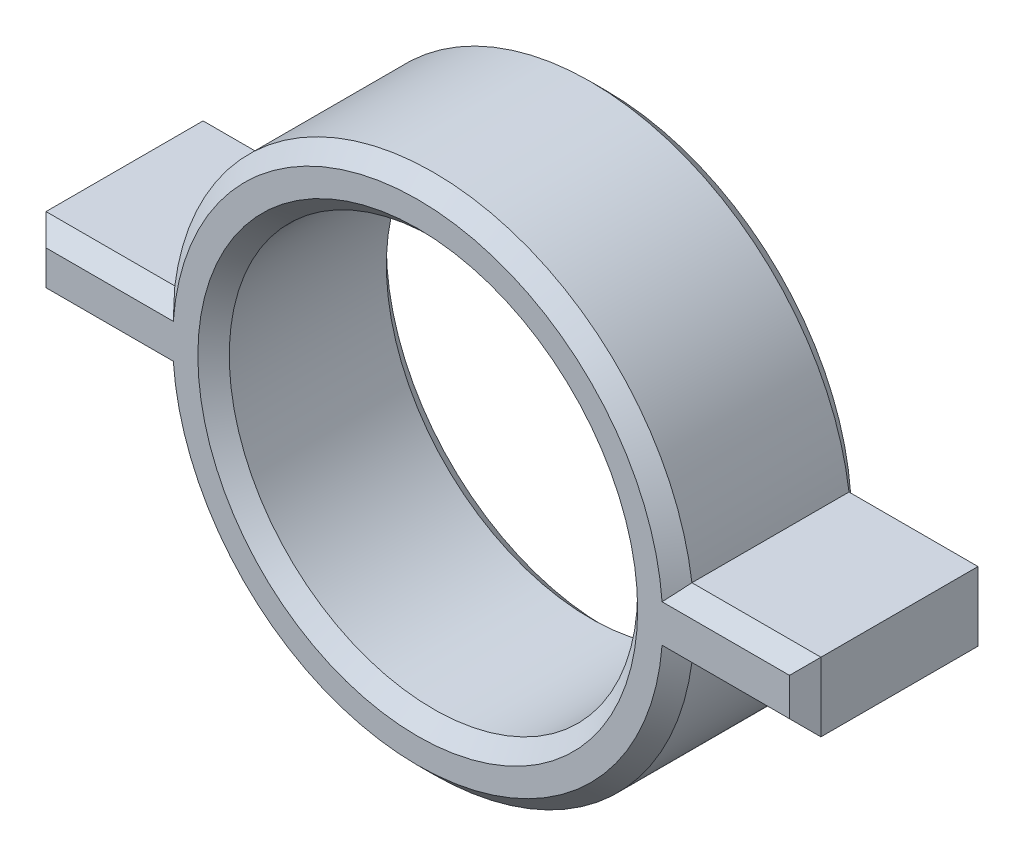
SolidWorks part; units mm, degrees
material "PLA"
ref_plane "Front Plane" through (0, 0, 0) normal (0, 0, 1) x (1, 0, 0)
ref_plane "Top Plane" through (0, 0, 0) normal (0, 1, 0) x (1, 0, 0)
ref_plane "Right Plane" through (0, 0, 0) normal (1, 0, 0) x (0, 0, -1)
sketch "Sketch1" plane through (0, 0, 0) normal (0, 0, 1) x (1, 0, 0)
  line L6 (8.227, -1.0985) -> (12.3333, -1.0985)
  line L7 (12.3333, -1.0985) -> (12.3333, 1.0985)
  line L8 (12.3333, 1.0985) -> (8.227, 1.0985)
  line L9 (-12.3333, 1.05) -> (-12.3333, -1.05)
  line L10 (-8.2333, 1.05) -> (-12.3333, 1.05)
  line L11 (-12.3333, -1.05) -> (-8.2333, -1.05)
  line L12 (0, 0) -> (16.0081, 0) construction
  line L13 (0, 0) -> (0, -4.3408) construction
  circle A1 centre (0, 0) radius 6.5 construction
  arc A4 (8.227, 1.0985) -> (-8.2333, 1.05) centre (0, 0) ccw
  arc A5 (-8.2333, -1.05) -> (8.227, -1.0985) centre (0, 0) ccw
  circle A6 centre (0, 0) radius 6.5
  dimension "D1" = 8.3
  dimension "D2" = 2.1
  dimension "D3" = 4.1
extrude "Boss-Extrude1" add sketch "Sketch1" along normal blind 6
chamfer "Chamfer1" distance 0.5 angle 45 18 edges at (6.5, 0, 0) (-12.3333, 0, 0) (-10.2833, -1.05, 0) (-0.0245, -8.3, 0) (10.2801, -1.0985, 0) (12.3333, 0, 0) (10.2801, 1.0985, 0) (-0.0245, 8.3, 0) (-10.2833, 1.05, 0) (6.5, 0, 6) (-0.0245, 8.3, 6) (10.2801, 1.0985, 6) (12.3333, 0, 6) (10.2801, -1.0985, 6) (-0.0245, -8.3, 6) (-10.2833, -1.05, 6) (-12.3333, 0, 6) (-10.2833, 1.05, 6)
